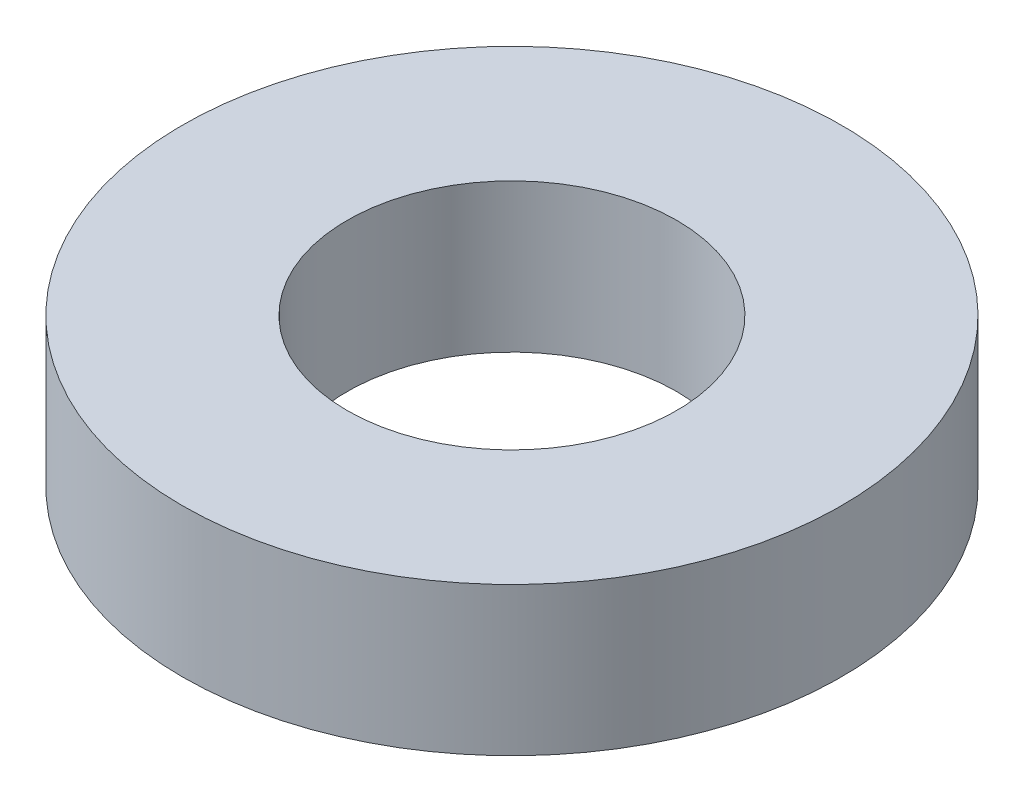
SolidWorks part; units mm, degrees
ref_plane "Front Plane" through (0, 0, 0) normal (0, 0, 1) x (1, 0, 0)
ref_plane "Top Plane" through (0, 0, 0) normal (0, 1, 0) x (1, 0, 0)
ref_plane "Right Plane" through (0, 0, 0) normal (1, 0, 0) x (0, 0, -1)
sketch "Sketch1" plane through (0, 0, 0) normal (0, 1, 0) x (1, 0, 0)
  circle A0 centre (0, 0) radius 20
  dimension "FLANGE_OD" = 40
extrude "Boss-Extrude1" add sketch "Sketch1" along normal blind 9
sketch "Sketch2" plane through (0, 0, 0) normal (0, 1, 0) x (1, 0, 0)
  circle A0 centre (0, 0) radius 10
  dimension "BORE_D" = 20
extrude "Cut-Extrude1" cut sketch "Sketch2" along normal through all
sketch "Sketch3" plane through (0, 9, 0) normal (0, 1, 0) x (1, 0, 0)
  circle A0 centre (0, 0) radius 7.3388 construction
  circle A1 centre (-7.3388, 0) radius 1.6309
  dimension "BOLT_D" = 3.2617
  dimension "BOLT_PCD" = 14.6777
extrude "Cut-Extrude2" cut sketch "Sketch3" against normal blind 7.32 rebuild error yes
pattern_circular "CirPattern1" count 6 over 360 rebuild error yes
